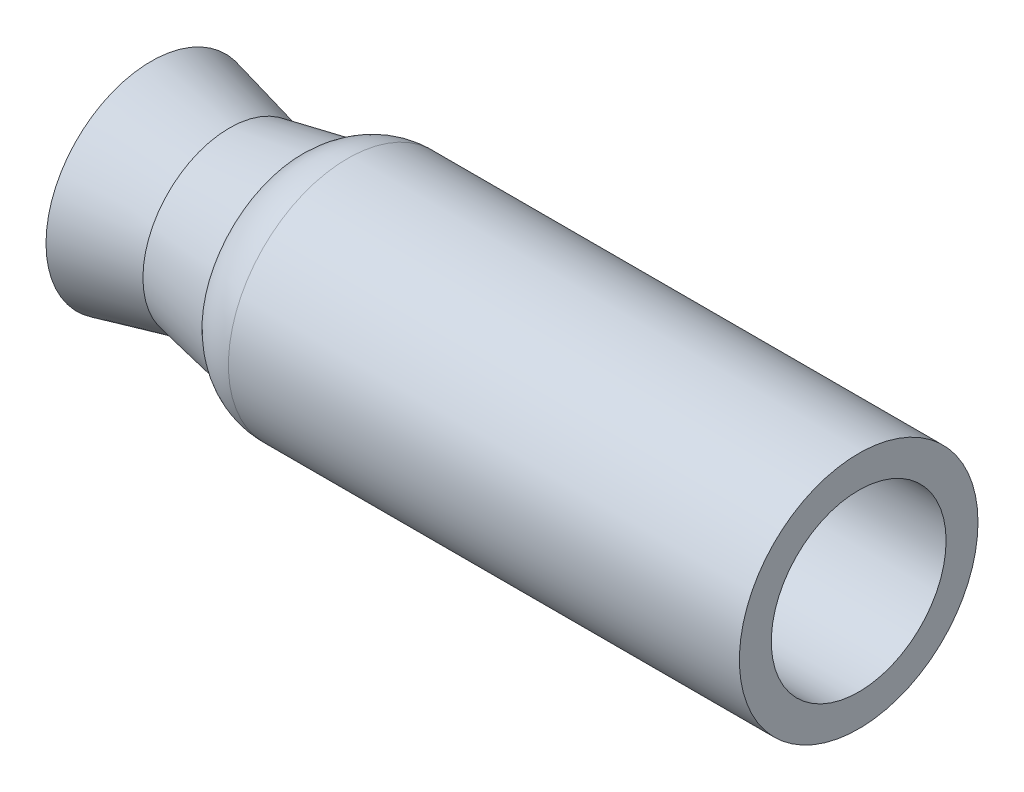
SolidWorks part; units mm, degrees
material "Thornel VCB-20 Carbon Cloth"
ref_plane "Front Plane" through (0, 0, 0) normal (0, 0, 1) x (1, 0, 0)
ref_plane "Top Plane" through (0, 0, 0) normal (0, 1, 0) x (1, 0, 0)
ref_plane "Right Plane" through (0, 0, 0) normal (1, 0, 0) x (0, 0, -1)
sketch "Sketch1" plane through (0, 0, 0) normal (0, 0, 1) x (1, 0, 0)
  line L0 (52.3226, 27.4009) -> (-107.8623, 27.4009)
  line L3 (0, 0) -> (-172.8085, 0) construction
  line L5 (-144.9334, 14.7) -> (-144.9334, 18.7) construction
  line L6 (-144.9334, 18.7) -> (-143.6334, 18.9501) construction
  line L7 (-169.4742, 32.9763) -> (-171.9334, 23.2835)
  line L8 (-122.0045, 31.5431) -> (-144.9334, 27.1315)
  line L10 (-107.8623, 37.4009) -> (52.3226, 37.4009)
  line L11 (52.3226, 37.4009) -> (52.3226, 27.4009)
  line L12 (-144.9334, 27.1315) -> (-169.4742, 32.9763)
  line L13 (-171.9334, 23.2835) -> (-187.0087, 27.1083) construction
  line L14 (-143.6334, 18.9501) -> (-143.6334, 14.2101)
  line L15 (-144.9334, 14.7) -> (-143.6334, 14.2101)
  line L16 (-143.6334, 18.9501) -> (-114.9334, 24.472)
  arc A0 (-107.8623, 27.4009) -> (-114.9334, 24.472) centre (-107.8623, 17.4009) ccw
  arc A5 (-107.8623, 37.4009) -> (-122.0045, 31.5431) centre (-107.8623, 17.4009) ccw
  parabola Q0 (-171.9334, 23.2835) -> (-144.9334, 14.7) focus (-225.4799, -74.885) apex (-225.7319, 30.0457)
  dimension "D1" = 10
  dimension "D7" = 30.0457
  dimension "D14" = 27.4009
  dimension "D16" = 167.256
  dimension "D3" = 37.4009
  dimension "D6" = 4
  dimension "D20" = 30
  dimension "D4" = 24.472
  dimension "D5" = 10
  dimension "D8" = 27
  dimension "D9" = 14.7
  dimension "D10" = 52.3226
  dimension "D11" = 23.2835
  dimension "D12" = 25.2272
  dimension "D13" = 4.74
  dimension "D15" = 28.7
  dimension "D19" = 10
revolve "Revolve1" add sketch "Sketch1" angle 360 about L3 region at (-59.566, 30.5813, 0)
equation "\"theta_t\"= 36.9009 - ( 426.271 / ( \"Aet\" + 7.00037 ) ) + ( 10026.8 / ( \"Aet\" + 7.00037 ) ^ 2 ) - ( 175410 / ( \"Aet\" + 7.00037 ) ^ 3 ) + ( ( 1.6742 * ( 10 ^ 6 ) ) / ( \"Aet\" + 7.00037 ) ^ 4 ) - ( ( 6.7643 * ( 10 ^ 6 ) ) / ( \"Aet\" + 7.00037 ) ^ 5 )"
equation "\"rt\"= ( 0.022412299 / 2 ) * 1000"
equation "\"re\"= sqr ( \"rt\" ^ 2 * \"Aet\" )"
equation "\"Aet\"= 4.317"
equation "\"L\"= 0.8 * ( ( \"re\" / tan ( 15 ) ) - ( \"rt\" / tan ( 15 ) ) )"
equation "\"lc\"= ( \"l*\" / \"cr\" )"
equation "\"b\"= tan ( \"theta_t\" )"
equation "\"a\"= ( \"re\" - \"b\" * \"L\" - \"c\" ) / \"L\" ^ 2"
equation "\"c\"= \"rt\" * ( 1.382 - 0.382 * cos ( \"theta_t\" ) )"
equation "\"cr\"= 5.978857531"
equation "\"rc\"= sqr ( \"cr\" * ( \"rt\" ^ 2 ) )"
equation "\"l*\"= 1000"
equation "\"th\"= 10"
equation "\"D19@Sketch1\"=\"th\""
equation "\"theta_cr\"= 45deg"
equation "\"D11@Sketch1\"=\"re\""
